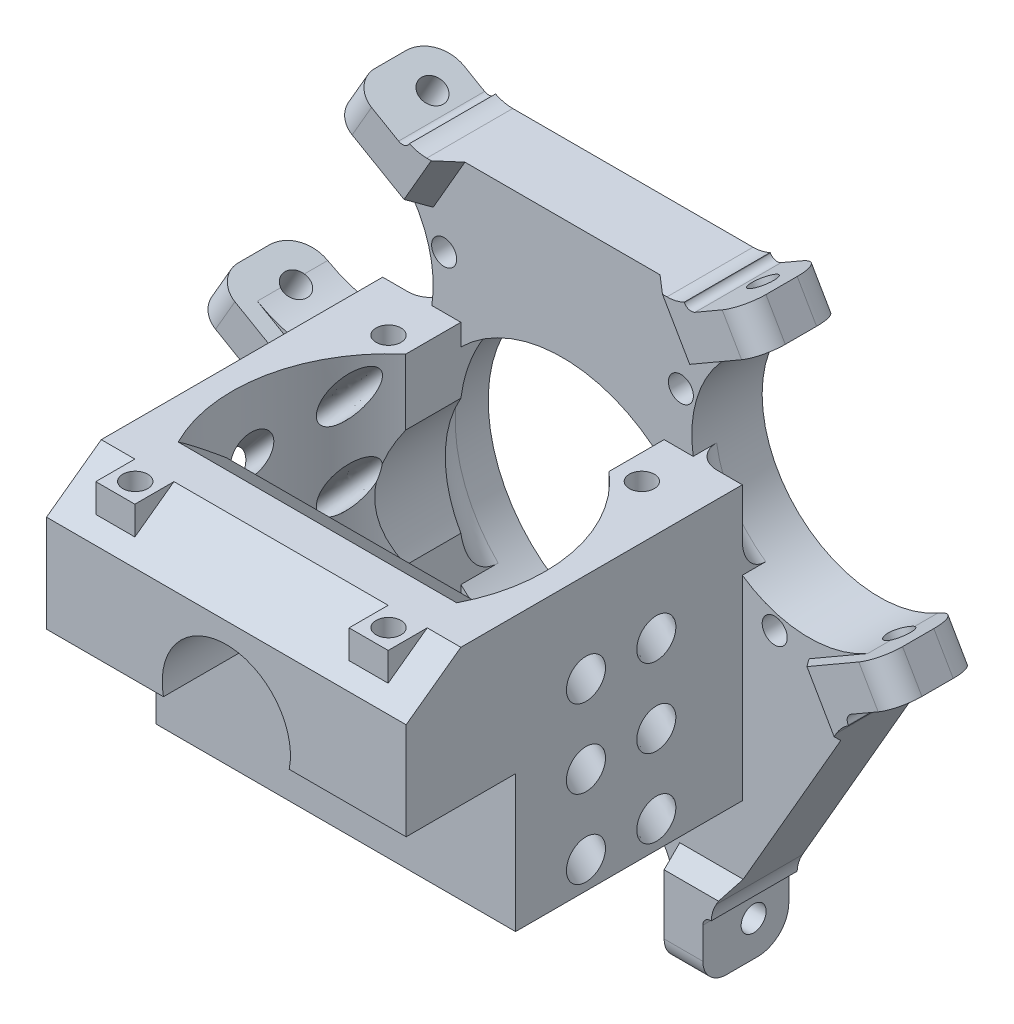
SolidWorks part; units mm, degrees
ref_plane "前基準面" through (0, 0, 0) normal (0, 0, 1) x (1, 0, 0)
ref_plane "上基準面" through (0, 0, 0) normal (0, 1, 0) x (1, 0, 0)
ref_plane "右基準面" through (0, 0, 0) normal (1, 0, 0) x (0, 0, -1)
sketch "草圖1" plane through (0, 0, 0) normal (0, 0, 1) x (1, 0, 0)
  line L0 (-34.4567, 17.2172) -> (-55.4567, -19.1558)
  line L1 (-30.9567, -61.5911) -> (11.0433, -61.5911)
  line L2 (35.5433, -19.1558) -> (14.5433, 17.2172)
  line L3 (60.0433, -61.5911) -> (-44.9567, -0.9693) construction
  line L4 (-9.9567, 59.6525) -> (-9.9567, -61.5911) construction
  line L5 (-79.9567, -61.5911) -> (25.0433, -0.9693) construction
  line L6 (-55.4567, -19.1558) -> (-47.6624, -23.6558)
  line L7 (-34.4567, 17.2172) -> (-26.6624, 12.7172)
  line L8 (-47.6624, -23.6558) -> (-30.9567, -52.5911)
  line L9 (27.7491, -23.6558) -> (11.0433, -52.5911)
  line L10 (-26.6624, 12.7172) -> (6.7491, 12.7172)
  line L11 (35.5433, -19.1558) -> (27.7491, -23.6558)
  line L13 (14.5433, 17.2172) -> (6.7491, 12.7172)
  line L16 (-30.9567, -61.5911) -> (-30.9567, -52.5911)
  line L17 (11.0433, -61.5911) -> (11.0433, -52.5911)
  circle A0 centre (-9.9567, -21.1766) radius 18.5
  point P8 (-51.5595, -21.4058)
  point P11 (-30.5595, 14.9672)
  dimension "D2" = 37
  dimension "D1" = 140
  dimension "D4" = 60
  dimension "D5" = 21
  dimension "D6" = 21
  dimension "D7" = 9
  dimension "D8" = 9
extrude "填料-伸長1" add sketch "草圖1" along normal blind 9
fillet "圓角1" radius 4 3 edges at (25.0433, -0.9693, 0) (-9.9567, -61.5911, 0) (-44.9567, -0.9693, 0)
sketch "草圖2" plane through (-22.1589, -38.3803, 0) normal (-0.5, -0.866, 0) x (0.866, -0.5, 0)
  line L1 (-29.449, 9) -> (-29.449, 0) construction
  line L2 (-38.449, 9) -> (-29.449, 9) construction
  circle A0 centre (-33.949, 4.5) radius 1.6
  dimension "D1" = 3.2
  dimension "D2" = 4.5
  dimension "D3" = 4.5
extrude "除料-伸長1" cut sketch "草圖2" against normal through all
sketch "草圖3" plane through (-30.9567, 0, 0) normal (-1, 0, 0) x (0, 0, 1)
  line L1 (9, -52.5911) -> (9, -61.5911) construction
  line L2 (9, -52.5911) -> (0, -52.5911) construction
  circle A0 centre (4.5, -57.0911) radius 1.6
  dimension "D1" = 3.2
  dimension "D2" = 4.5
  dimension "D3" = 4.5
extrude "除料-伸長2" cut sketch "草圖3" against normal through all
sketch "草圖4" plane through (17.1806, -29.7576, 0) normal (0.5, -0.866, 0) x (0.866, 0.5, 0)
  line L1 (12.2035, 9) -> (21.2035, 9) construction
  line L2 (12.2035, 9) -> (12.2035, 0) construction
  circle A0 centre (16.7035, 4.5) radius 1.6
  dimension "D1" = 3.2
  dimension "D2" = 4.5
  dimension "D3" = 4.5
extrude "除料-伸長3" cut sketch "草圖4" against normal through all
fillet "圓角2" radius 5 6 edges at (-30.9567, -52.5911, 4.5) (-47.6624, -23.6558, 4.5) (-26.6624, 12.7172, 4.5) (6.7491, 12.7172, 4.5) (11.0433, -52.5911, 4.5) (27.7491, -23.6558, 4.5)
sketch "草圖9" plane through (0, 0, 0) normal (0, 0, -1) x (-1, 0, 0)
  line L0 (-11.0433, -57.5911) -> (30.9567, -57.5911) construction
  line L1 (24.9567, -57.5911) -> (24.9567, -63.5464)
  line L2 (24.9567, -63.5464) -> (-5.0433, -63.5464)
  line L3 (-5.0433, -63.5464) -> (-5.0433, -57.5911)
  line L4 (-34.2367, -12.982) -> (-19.2367, 12.9987)
  line L5 (-19.2367, 12.9987) -> (-14.0792, 10.0211)
  line L6 (-29.0792, -15.9597) -> (-34.2367, -12.982)
  line L7 (39.15, 12.9987) -> (54.15, -12.982)
  line L8 (54.15, -12.982) -> (48.9926, -15.9597)
  line L9 (33.9926, 10.0211) -> (39.15, 12.9987)
  arc A0 (24.9567, -57.5911) -> (-5.0433, -57.5911) centre (9.9567, -57.5911) ccw
  arc A1 (-29.0792, -15.9597) -> (-14.0792, 10.0211) centre (-21.5792, -2.9693) ccw
  arc A2 (33.9926, 10.0211) -> (48.9926, -15.9597) centre (41.4926, -2.9693) ccw
  point P11 (9.9567, -21.1766)
  point P21 (9.9567, -21.1766)
  dimension "D1" = 3
extrude "除料-伸長7" cut sketch "草圖9" against normal through all
sketch "草圖10" plane through (0, 0, 0) normal (0, 0, -1) x (-1, 0, 0)
  line L0 (-5.0433, -57.5911) -> (-5.0433, -42.5911) construction
  line L1 (-5.0433, -42.5911) -> (24.9567, -42.5911) construction
  line L2 (24.9567, -42.5911) -> (24.9567, -57.5911) construction
  line L3 (9.9567, -42.5911) -> (9.9567, -70.7856) construction
  circle A0 centre (-2.0433, -45.5911) radius 1.6
  circle A1 centre (21.9567, -45.5911) radius 1.6
  circle A2 centre (-5.1869, 1.423) radius 1.6
  circle A3 centre (-17.1869, -19.3616) radius 1.6
  circle A4 centre (37.1003, -19.3616) radius 1.6
  circle A5 centre (25.1003, 1.423) radius 1.6
  point P23 (9.9567, -21.1766)
  dimension "D3" = 3
  dimension "D7" = 3.2
  dimension "D1" = 15
  dimension "D2" = 30
  dimension "D4" = 3
  dimension "D6" = 24
  dimension "D5" = 3
extrude "除料-伸長8" cut sketch "草圖10" against normal blind 9
sketch "草圖24" plane through (0, 0, 0) normal (1, 0, 0) x (0, 0, -1)
  line L0 (-11.2262, 6.4815) -> (0, 0) construction
  line L1 (0, 0) -> (0, 20.5715) construction
  dimension "D1" = 60
sketch "草圖27" plane through (0, 0, 9) normal (0, 0, 1) x (1, 0, 0)
  line L0 (-9.9567, 12.7172) -> (-9.9567, -42.5911) construction
  line L1 (5.4094, 12.7172) -> (-25.3227, 12.7172) construction
  line L2 (13.0433, -40.2828) -> (3.0433, -40.2828)
  line L3 (-32.9567, -5.2828) -> (-22.9567, -5.2828)
  line L4 (-32.9567, -5.2828) -> (-32.9567, -40.2828)
  line L5 (-32.9567, -40.2828) -> (-22.9567, -40.2828)
  line L6 (-22.9567, -5.2828) -> (-22.9567, -40.2828)
  line L7 (3.0433, -5.2828) -> (3.0433, -40.2828)
  line L8 (13.0433, -5.2828) -> (3.0433, -5.2828)
  line L9 (13.0433, -5.2828) -> (13.0433, -40.2828)
  arc A0 (5.0433, -57.5911) -> (-24.9567, -57.5911) centre (-9.9567, -57.5911) ccw construction
  dimension "D1" = 35
  dimension "D2" = 10
  dimension "D3" = 18
  dimension "D4" = 13
extrude "填料-伸長2" add sketch "草圖27" along normal blind 23
sketch "草圖28" plane through (0, -5.2828, 0) normal (0, 1, 0) x (1, 0, 0)
  line L0 (-9.9567, -9) -> (-9.9567, -11.25) construction
  line L2 (5.4094, -9) -> (-25.3227, -9) construction
  line L6 (-9.9567, -11.25) -> (-9.9567, -51.25) construction
  circle A0 centre (-9.9567, -31.25) radius 20
  dimension "D1" = 2.25
  dimension "D2" = 40
extrude "除料-伸長19" cut sketch "草圖28" against normal through all
sketch "草圖29" plane through (0, -5.2828, 0) normal (0, 1, 0) x (1, 0, 0)
  line L0 (-9.9567, -9) -> (-9.9567, -43.4242) construction
  line L1 (5.4094, -9) -> (-25.3227, -9) construction
  line L2 (-9.9567, -43.4242) -> (-29.9567, -43.4242) construction
  line L3 (-29.9567, -43.4242) -> (-29.9567, -9) construction
  line L4 (-26.672, -9) -> (-32.9567, -9) construction
  line L5 (-9.9567, -11.25) -> (-29.9567, -11.25) construction
  circle A0 centre (-26.1567, -15.05) radius 1.6
  circle A1 centre (6.2433, -15.05) radius 1.6
  dimension "D1" = 2.25
  dimension "D3" = 3.8
  dimension "D4" = 3.2
  dimension "D2" = 3.8
extrude "除料-伸長20" cut sketch "草圖29" against normal blind 10
sketch "草圖30" plane through (0, 0, 32) normal (0, 0, 1) x (1, 0, 0)
  line L2 (13.0433, -40.2828) -> (-32.9567, -40.2828)
  line L3 (13.0433, -40.2828) -> (13.0433, -5.2828)
  line L4 (13.0433, -5.2828) -> (-32.9567, -5.2828)
  line L5 (-32.9567, -40.2828) -> (-32.9567, -5.2828)
  circle A0 centre (-9.9567, -21.1766) radius 8.2
  dimension "D1" = 16.4
  dimension "D2" = 46
extrude "填料-伸長3" add sketch "草圖30" along normal blind 6
sketch "草圖31" plane through (0, 0, 38) normal (0, 0, 1) x (1, 0, 0)
  line L0 (-32.9567, -22.7828) -> (-17.9978, -22.7828)
  line L1 (-32.9567, -5.2828) -> (-32.9567, -40.2828) construction
  line L2 (13.0433, -40.2828) -> (13.0433, -5.2828) construction
  line L3 (13.0433, -22.7828) -> (13.0433, -5.2828)
  line L4 (13.0433, -5.2828) -> (-32.9567, -5.2828)
  line L5 (-32.9567, -5.2828) -> (-32.9567, -22.7828)
  line L6 (-1.9155, -22.7828) -> (13.0433, -22.7828)
  arc A0 (-1.9155, -22.7828) -> (-17.9978, -22.7828) centre (-9.9567, -21.1766) ccw
  dimension "D1" = 17.5
extrude "填料-伸長4" add sketch "草圖31" along normal blind 14
chamfer "導角1" distance 7 angle 36 1 edges at (-9.9567, -5.2828, 52) first distance on face at (-27.7567, -5.2828, 15.05)
chamfer "導角2" distance 7 angle 50 1 edges at (-9.9567, -5.2828, 32) first distance on face at (-9.9567, -22.7828, 32)
sketch "草圖33" plane through (0, -5.2828, 0) normal (0, 1, 0) x (1, 0, 0)
  line L0 (-9.9567, -9) -> (-9.9567, -11.25) construction
  line L1 (5.4094, -9) -> (-25.3227, -9) construction
  line L2 (-9.9567, -11.25) -> (-9.9567, -51.25) construction
  line L3 (-9.9567, -51.25) -> (-29.9567, -51.25) construction
  line L4 (-29.9567, -51.25) -> (-29.9567, -9) construction
  line L5 (-27.8227, -9) -> (-34.4567, -9) construction
  circle A0 centre (-26.1567, -47.45) radius 1.6
  circle A1 centre (6.2433, -47.45) radius 1.6
  dimension "D6" = 3.2
  dimension "D1" = 40
  dimension "D2" = 2.25
  dimension "D3" = 20
  dimension "D4" = 3.8
  dimension "D5" = 3.8
extrude "除料-伸長21" cut sketch "草圖33" against normal blind 10
sketch "草圖34" plane through (0, -22.7828, 0) normal (0, -1, 0) x (1, 0, 0)
  line L0 (-32.9567, 52) -> (-32.9567, 38) construction
  line L1 (-32.9567, 38) -> (-17.9978, 38) construction
  line L2 (-17.9978, 52) -> (-17.9978, 38) construction
  line L3 (-32.9567, 38) -> (13.0433, 38) construction
  line L4 (-9.9567, 38) -> (-9.9567, 52) construction
  line L5 (-1.7567, 52) -> (-18.1567, 52) construction
  circle A0 centre (-29.9567, 43) radius 1.6
  circle A1 centre (-21.9978, 43) radius 1.6
  circle A2 centre (10.0433, 43) radius 1.6
  circle A3 centre (2.0845, 43) radius 1.6
  dimension "D1" = 3.2
  dimension "D4" = 3.2
  dimension "D2" = 3
  dimension "D3" = 5
  dimension "D5" = 4
  dimension "D6" = 5
  dimension "D7" = 7.9588
extrude "除料-伸長22" cut sketch "草圖34" against normal blind 10
sketch "草圖35" plane through (0, 0, 38) normal (0, 0, 1) x (1, 0, 0)
  line L0 (-32.9567, -15.3037) -> (-32.9567, -40.2828) construction
  line L1 (-32.9567, -22.7828) -> (-17.9978, -22.7828) construction
  line L2 (-9.9567, -12.9766) -> (-9.9567, -40.2828) construction
  line L3 (-32.9567, -40.2828) -> (13.0433, -40.2828) construction
  circle A0 centre (-26.5567, -26.7828) radius 1.6
  arc A1 (-1.9155, -22.7828) -> (-17.9978, -22.7828) centre (-9.9567, -21.1766) ccw construction
  circle A2 centre (6.6433, -26.7828) radius 1.6
  dimension "D1" = 3.2
  dimension "D2" = 6.4
  dimension "D3" = 4
extrude "除料-伸長23" cut sketch "草圖35" against normal blind 10
sketch "草圖36" plane through (-32.9567, 0, 0) normal (-1, 0, 0) x (0, 0, 1)
  line L0 (45, -5.2828) -> (9, -5.2828) construction
  line L1 (38, -22.7828) -> (38, -40.2828) construction
  circle A0 centre (29, -16.7828) radius 2.5
  circle A1 centre (20, -16.7828) radius 2.5
  circle A3 centre (20, -26.7828) radius 2.5
  circle A5 centre (20, -36.7828) radius 2.5
  circle A7 centre (29, -26.7828) radius 2.5
  circle A8 centre (29, -36.7828) radius 2.5
  dimension "D1" = 5
  dimension "D2" = 11.5
  dimension "D3" = 9
  dimension "D6" = 9
  dimension "D4" = 2
  dimension "D5" = 3
sketch "草圖37" plane through (0, 0, 38) normal (0, 0, 1) x (1, 0, 0)
  line L0 (-9.9567, -5.2828) -> (-9.9567, -40.2828) construction
  line L3 (-9.9567, -5.2828) -> (18.606, -35.9124) construction
  line L4 (-9.9567, -5.2828) -> (-38.5193, -35.9124) construction
  dimension "D1" = 43
  dimension "D2" = 43
extrude "除料-伸長24" cut sketch "草圖36" along direction (-0.682, -0.7314, 0) on the side against the normal through all
sketch "草圖38" plane through (13.0433, 0, 0) normal (1, 0, 0) x (0, 0, -1)
  line L0 (-45, -5.2828) -> (-9, -5.2828) construction
  line L1 (-38, -5.2828) -> (-38, -35.9124) construction
  circle A0 centre (-29, -16.7828) radius 2.5
  circle A1 centre (-20, -16.7828) radius 2.5
  circle A3 centre (-20, -26.7828) radius 2.5
  circle A5 centre (-20, -36.7828) radius 2.5
  circle A7 centre (-29, -26.7828) radius 2.5
  circle A8 centre (-29, -36.7828) radius 2.5
  dimension "D1" = 5
  dimension "D2" = 11.5
  dimension "D3" = 9
  dimension "D6" = 9
  dimension "D4" = 2
  dimension "D5" = 3
extrude "除料-伸長25" cut sketch "草圖38" along direction (0.682, -0.7314, 0) on the side against the normal through all
sketch "草圖40" plane through (0, 0, 0) normal (0, 0, -1) x (-1, 0, 0)
  circle A0 centre (9.9567, -21.1766) radius 15
  dimension "D1" = 30
extrude "除料-伸長27" cut sketch "草圖40" against normal blind 26
fillet "圓角3" radius 5 2 edges at (-28.4567, -21.1766, 9) (8.5433, -21.1766, 9)
fillet "圓角4" radius 3 2 edges at (8.8715, -10.9389, 9) (-28.7849, -10.9389, 9)
sketch "草圖41" plane through (0, -5.2828, 0) normal (0, 1, 0) x (1, 0, 0)
  line L0 (8.7433, -45) -> (8.7433, -50)
  line L1 (-32.9567, -45) -> (13.0433, -45) construction
  line L2 (8.7433, -50) -> (3.7433, -50)
  line L3 (3.7433, -50) -> (3.7433, -45)
  line L4 (3.7433, -45) -> (8.7433, -45)
  line L5 (-9.9567, -45) -> (-9.9567, -52) construction
  line L6 (13.0433, -52) -> (-32.9567, -52) construction
  line L7 (13.0433, -45) -> (13.0433, -52) construction
  line L8 (-28.6567, -45) -> (-28.6567, -50)
  line L9 (-23.6567, -45) -> (-28.6567, -45)
  line L10 (-23.6567, -50) -> (-23.6567, -45)
  line L11 (-28.6567, -50) -> (-23.6567, -50)
  circle A0 centre (6.2433, -47.45) radius 1.6
  circle A1 centre (-26.1567, -47.45) radius 1.6
  dimension "D1" = 3.2
  dimension "D2" = 5
  dimension "D3" = 5
  dimension "D4" = 4.3
  dimension "D5" = 2.5
  dimension "D6" = 2.5
extrude "填料-伸長5" add sketch "草圖41" against normal blind 10
sketch "草圖42" plane through (0, 0, 38) normal (0, 0, 1) x (1, 0, 0)
  line L0 (-32.9567, -22.7828) -> (13.0433, -22.7828) construction
  line L1 (13.0433, -40.2828) -> (13.0433, -15.3037) construction
  line L2 (13.0433, -22.7828) -> (13.0433, -10.3686) construction
  arc A0 (-17.9978, -22.7828) -> (-1.9155, -22.7828) centre (-9.9567, -21.1766) ccw construction
  point P10 (-9.9567, -29.3766)
  dimension "D1" = 6.5938
sketch "草圖46" plane through (0, 0, 9) normal (0, 0, 1) x (1, 0, 0)
  line L0 (14.5433, 17.2172) -> (7.9094, 13.3871)
  line L1 (7.9094, 13.3871) -> (10.9094, 8.191)
  line L2 (14.5433, 17.2172) -> (17.5433, 12.0211)
  line L3 (17.5433, 12.0211) -> (10.9094, 8.191)
  line L4 (-9.9567, 12.7172) -> (-9.9567, -5.2828) construction
  line L5 (5.4094, 12.7172) -> (-25.3227, 12.7172) construction
  line L6 (-23.6567, -5.2828) -> (3.7433, -5.2828) construction
  line L7 (-37.4567, 12.0211) -> (-30.8227, 8.191)
  line L8 (-34.4567, 17.2172) -> (-37.4567, 12.0211)
  line L9 (-27.8227, 13.3871) -> (-30.8227, 8.191)
  line L10 (-34.4567, 17.2172) -> (-27.8227, 13.3871)
  line L11 (5.0433, -61.5911) -> (5.0433, -53.9308)
  line L12 (11.0433, -61.5911) -> (5.0433, -61.5911)
  line L13 (11.0433, -61.5911) -> (11.0433, -53.9308)
  line L14 (11.0433, -53.9308) -> (5.0433, -53.9308)
  line L15 (35.5433, -19.1558) -> (28.9094, -22.986)
  line L16 (28.9094, -22.986) -> (25.9094, -17.7898)
  line L17 (32.5433, -13.9597) -> (25.9094, -17.7898)
  line L18 (35.5433, -19.1558) -> (32.5433, -13.9597)
  line L19 (-52.4567, -13.9597) -> (-45.8227, -17.7898)
  line L20 (-55.4567, -19.1558) -> (-52.4567, -13.9597)
  line L21 (-55.4567, -19.1558) -> (-48.8227, -22.986)
  line L22 (-48.8227, -22.986) -> (-45.8227, -17.7898)
  line L23 (-30.9567, -61.5911) -> (-30.9567, -53.9308)
  line L24 (-30.9567, -53.9308) -> (-24.9567, -53.9308)
  line L25 (-24.9567, -61.5911) -> (-24.9567, -53.9308)
  line L26 (-30.9567, -61.5911) -> (-24.9567, -61.5911)
  point P35 (-9.9567, -21.1766)
  dimension "D1" = 3
extrude "填料-伸長7" add sketch "草圖46" along normal blind 2
chamfer "導角3" distance 5 angle 45 6 edges at (9.4094, 10.789, 9) (-29.3227, 10.789, 9) (-47.3227, -20.3879, 9) (-27.9567, -53.9308, 9) (8.0433, -53.9308, 9) (27.4094, -20.3879, 9)
fillet "圓角5" radius 3 6 edges at (8.0433, -61.5911, 11) (-27.9567, -61.5911, 11) (-53.9567, -16.5578, 11) (-35.9567, 14.6192, 11) (34.0433, -16.5578, 11) (16.0433, 14.6192, 11)
sketch "草圖47" plane through (0, 0, 9) normal (0, 0, 1) x (1, 0, 0)
  line L1 (-26.7336, 24.594) -> (-57.9836, -29.5326) construction
  line L2 (-9.9567, -21.1766) -> (-42.3586, -2.4693) construction
  line L3 (-34.4567, 17.2172) -> (-34.9817, 16.3079)
  line L4 (-37.4567, 12.0211) -> (-34.4567, 17.2172) construction
  line L6 (-34.9817, 16.3079) -> (-28.0535, 12.3079)
  line L8 (-28.0535, 12.3079) -> (-25.9335, 15.9798)
  line L9 (-25.9335, 15.9798) -> (-32.8617, 19.9798)
  line L10 (-32.8617, 19.9798) -> (-34.4567, 17.2172)
  line L11 (-31.8586, 15.7172) -> (-34.4567, 17.2172) construction
  line L12 (-57.0516, -21.9184) -> (-55.4567, -19.1558)
  line L13 (-50.1234, -25.9184) -> (-57.0516, -21.9184)
  line L14 (-48.0035, -22.2465) -> (-50.1234, -25.9184)
  line L15 (-54.9317, -18.2465) -> (-48.0035, -22.2465)
  line L16 (-55.4567, -19.1558) -> (-54.9317, -18.2465)
  line L17 (30.2101, -25.9184) -> (37.1383, -21.9184)
  line L18 (28.0901, -22.2465) -> (30.2101, -25.9184)
  line L19 (35.0183, -18.2465) -> (28.0901, -22.2465)
  line L20 (35.5433, -19.1558) -> (35.0183, -18.2465)
  line L21 (37.1383, -21.9184) -> (35.5433, -19.1558)
  line L22 (12.9484, 19.9798) -> (14.5433, 17.2172)
  line L23 (14.5433, 17.2172) -> (15.0683, 16.3079)
  line L24 (15.0683, 16.3079) -> (8.1401, 12.3079)
  line L25 (8.1401, 12.3079) -> (6.0202, 15.9798)
  line L26 (6.0202, 15.9798) -> (12.9484, 19.9798)
  line L27 (-34.1466, -53.5911) -> (-34.1466, -61.5911)
  line L28 (-29.9067, -53.5911) -> (-34.1466, -53.5911)
  line L29 (-29.9067, -61.5911) -> (-29.9067, -53.5911)
  line L30 (-30.9567, -61.5911) -> (-29.9067, -61.5911)
  line L31 (-34.1466, -61.5911) -> (-30.9567, -61.5911)
  line L32 (14.2333, -61.5911) -> (11.0433, -61.5911)
  line L33 (11.0433, -61.5911) -> (9.9933, -61.5911)
  line L34 (9.9933, -61.5911) -> (9.9933, -53.5911)
  line L35 (9.9933, -53.5911) -> (14.2333, -53.5911)
  line L36 (14.2333, -53.5911) -> (14.2333, -61.5911)
  point P5 (-42.3586, -2.4693)
  point P10 (-26.7336, 24.594)
  point P42 (-9.9567, -21.1766)
  point P47 (-9.9567, -21.1766)
  dimension "D1" = 62.5
  dimension "D2" = 1.05
  dimension "D3" = 8
extrude "除料-伸長28" cut sketch "草圖47" against normal through all both and the other way through all
fillet "圓角7" radius 1 6 edges at (8.1401, 12.3079, 5.5) (28.0901, -22.2465, 5.5) (9.9933, -53.5911, 5.5) (-29.9067, -53.5911, 5.5) (-48.0035, -22.2465, 5.5) (-28.0535, 12.3079, 5.5)
